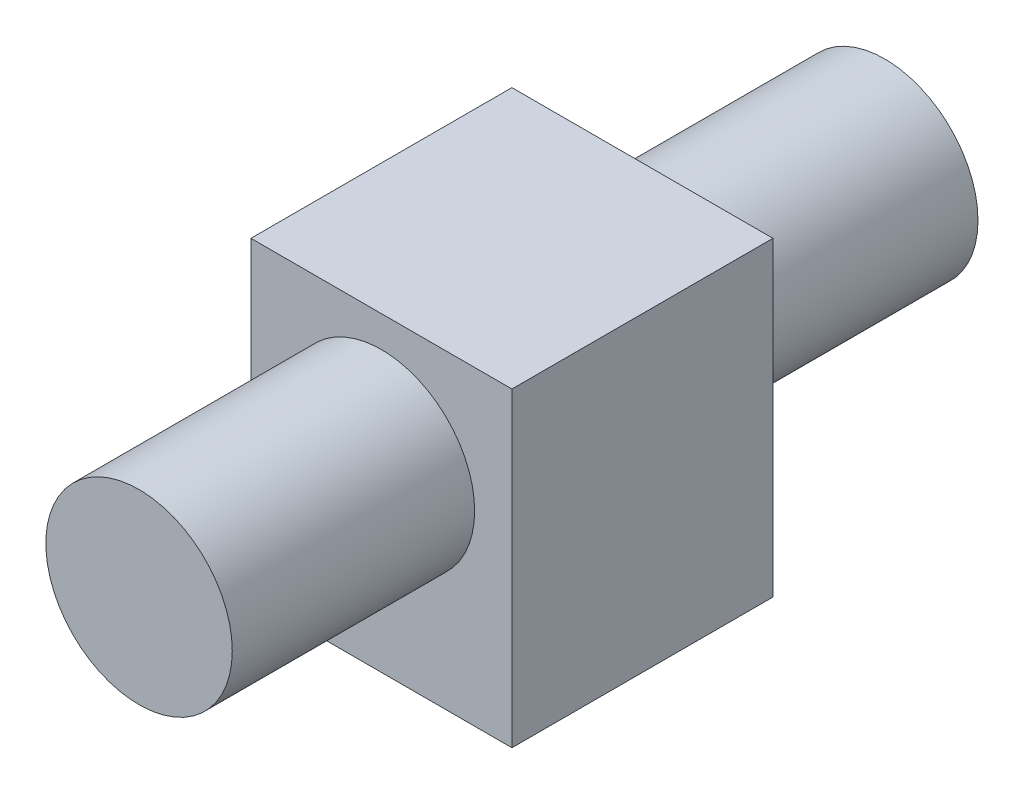
SolidWorks part; units mm, degrees
ref_plane "前视基准面" through (0, 0, 0) normal (0, 0, 1) x (1, 0, 0)
ref_plane "上视基准面" through (0, 0, 0) normal (0, 1, 0) x (1, 0, 0)
ref_plane "右视基准面" through (0, 0, 0) normal (1, 0, 0) x (0, 0, -1)
other "Configuration Table"
sketch "Sketch1" plane through (0, 0, 0) normal (0, 1, 0) x (1, 0, 0)
  line L1 (-21, -21) -> (21, -21)
  line L2 (-21, -21) -> (-21, 21)
  line L3 (-21, 21) -> (21, 21)
  line L4 (21, -21) -> (21, 21)
  line L5 (-21, -21) -> (21, 21) construction
  line L6 (-21, 21) -> (21, -21) construction
  point P0 (0, 0)
extrude "Boss-Extrude1" add sketch "Sketch1" along normal blind 50
sketch "Sketch2" plane through (0, 0, 0) normal (0, 0, 1) x (1, 0, 0)
  circle A0 centre (0, 30) radius 15
extrude "Boss-Extrude2" add sketch "Sketch2" along normal blind 60 and the other way blind 60
sketch3d "3DSketch1"
  line L0 (0, 0, 0) -> (0, 100, 0) construction
ref_axis "Axis_J1" through (0, 0, 0) along (0, 1, 0)
sketch3d "3DSketch2"
  line L0 (0, 30, 0) -> (0, 30, 100) construction
ref_axis "Axis_J2" through (0, 30, 0) along (0, 0, 1)
ref_plane "Mate_Bottom" through (0, 0, 0) normal (0, 1, 0) x (1, 0, 0)
ref_plane "Mate_Mid" through (0, 0, 0) normal (0, 0, 1) x (1, 0, 0)
